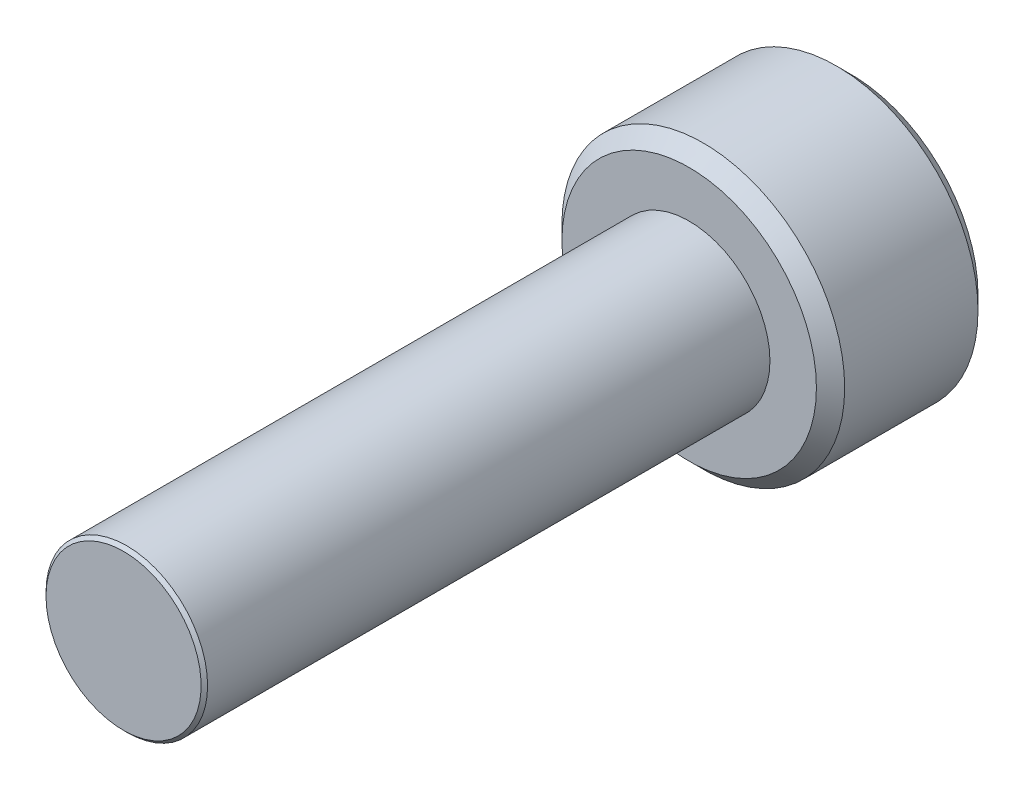
SolidWorks part; units mm, degrees
ref_plane "Front Plane" through (0, 0, 0) normal (0, 0, 1) x (1, 0, 0)
ref_plane "Top Plane" through (0, 0, 0) normal (0, 1, 0) x (1, 0, 0)
ref_plane "Right Plane" through (0, 0, 0) normal (1, 0, 0) x (0, 0, -1)
sketch "Sketch1" plane through (0, 0, 0) normal (0, 0, 1) x (1, 0, 0)
  circle A0 centre (0, 0) radius 2
  dimension "OD" = 4
extrude "Extrude1" add sketch "Sketch1" against normal blind 14
sketch "Sketch2" plane through (0, 0, 0) normal (0, 0, 1) x (1, 0, 0)
  circle A0 centre (0, 0) radius 2 construction
  circle A1 centre (0, 0) radius 2
curve "Helix/Spiral1" pitch 0.7 height 14.7 radius 2 centre (0, 0, 0) axis (0, 0, -1) start towards (0, 1, 0) parameters "pitch"=0.7
sketch "Sketch3" plane through (0, 0, 0) normal (1, 0, 0) x (0, 0, -1)
  line L0 (-0.6125, 2) -> (-0.35, 1.5453)
  line L1 (-0.35, 1.5453) -> (-0.2625, 1.5453)
  line L2 (-0.2625, 1.5453) -> (0, 2)
  line L3 (-0.6125, 2) -> (0, 2)
  line L4 (-0.3062, 2) -> (-0.3062, 1.5453) construction
  line L5 (-0.4812, 1.7727) -> (-0.1312, 1.7727) construction
  line L6 (0, 2) -> (0, -2) construction
  dimension "D1" = 0.0875
  dimension "D2" = 0.35
  dimension "D3" = 60
sweep "Cut-Sweep1" cut profiles "Sketch3" path "Helix/Spiral1" align with end faces yes
sketch "Sketch4" plane through (0, 0, 0) normal (1, 0, 0) x (0, 0, -1)
  line L0 (0.4962, 2) -> (0, 1.2913)
  line L1 (0, 1.2913) -> (0, 2)
  line L2 (0.4962, 2) -> (0, 2)
  line L3 (-0.6125, 2) -> (0, 2) construction
  line L4 (0, 0) -> (7.0209, 0) construction
  dimension "D1" = 55
  dimension "D2" = 0.254
revolve "Cut-Revolve1" cut sketch "Sketch4" angle 360 about L4
sketch "Sketch6" plane through (0, 0, -14) normal (0, 0, -1) x (-1, 0, 0)
  circle A0 centre (0, 0) radius 3.5
  dimension "head dia" = 7
extrude "Extrude2" add sketch "Sketch6" along normal blind 4
sketch "Sketch7" plane through (0, 0, -18) normal (0, 0, -1) x (-1, 0, 0)
  line L1 (0, 1.7321) -> (-1.5, 0.866)
  line L2 (-1.5, 0.866) -> (-1.5, -0.866)
  line L3 (-1.5, -0.866) -> (0, -1.7321)
  line L4 (0, -1.7321) -> (1.5, -0.866)
  line L5 (1.5, -0.866) -> (1.5, 0.866)
  line L6 (1.5, 0.866) -> (0, 1.7321)
  circle A0 centre (0, 0) radius 1.5 construction
  dimension "hex dia" = 3
extrude "Cut-Extrude1" cut sketch "Sketch7" against normal blind 2.25
sketch "Sketch8" plane through (0, 0, -18) normal (0, 0, -1) x (-1, 0, 0)
  circle A0 centre (0, 0) radius 1.7321
extrude "Cut-Extrude2" cut sketch "Sketch8" against normal through all draft 45
chamfer "Chamfer1" distance 0.35 angle 45 2 edges at (-3.5, 0, -18) (-3.5, 0, -14)
sketch "Sketch10" plane through (0, 0, -14) normal (0, 0, 1) x (1, 0, 0)
  circle A1 centre (0, 0) radius 2
  circle A2 centre (0, 0) radius 2
  dimension "D1" = 0
ref_plane "Plane1" through (0, 0, 0) normal (0, 0, 1) x (1, 0, 0)
extrude "partial thread" add sketch "Sketch10" along normal up to surface (14 mm away) separate body up to plane "Plane1"
chamfer "Chamfer2" distance 0.08 angle 45 1 edges at (2, 0, 0)
combine bodies "Combine1" operation type add bodies to combine 107 108
sketch "Sketch9" plane through (0, 0, 0) normal (1, 0, 0) x (0, 0, -1)
  line L0 (0, 2) -> (0, -2) construction
  line L1 (1.75, 2) -> (1.75, -2) construction
  dimension "D1" = 1.75
equation "\"D3@Helix/Spiral1\" = \"screw length@Extrude1\"+\"pitch@Helix/Spiral1\""
equation "\"D1@Sketch3\" = \"pitch@Helix/Spiral1\"*.125"
equation "\"D2@Sketch3\" = \"pitch@Helix/Spiral1\"*.5"
equation "\"D1@Cut-Extrude1\" = \"hex dia@Sketch7\"*.75"
equation "\"D1@Chamfer1\" = \"head dia@Sketch6\"*.05"
equation "\"D1@Sketch9\" = \"pitch@Helix/Spiral1\"*2.5"
equation "\"D1@Chamfer2\"=\"OD@Sketch1\"*.02"
